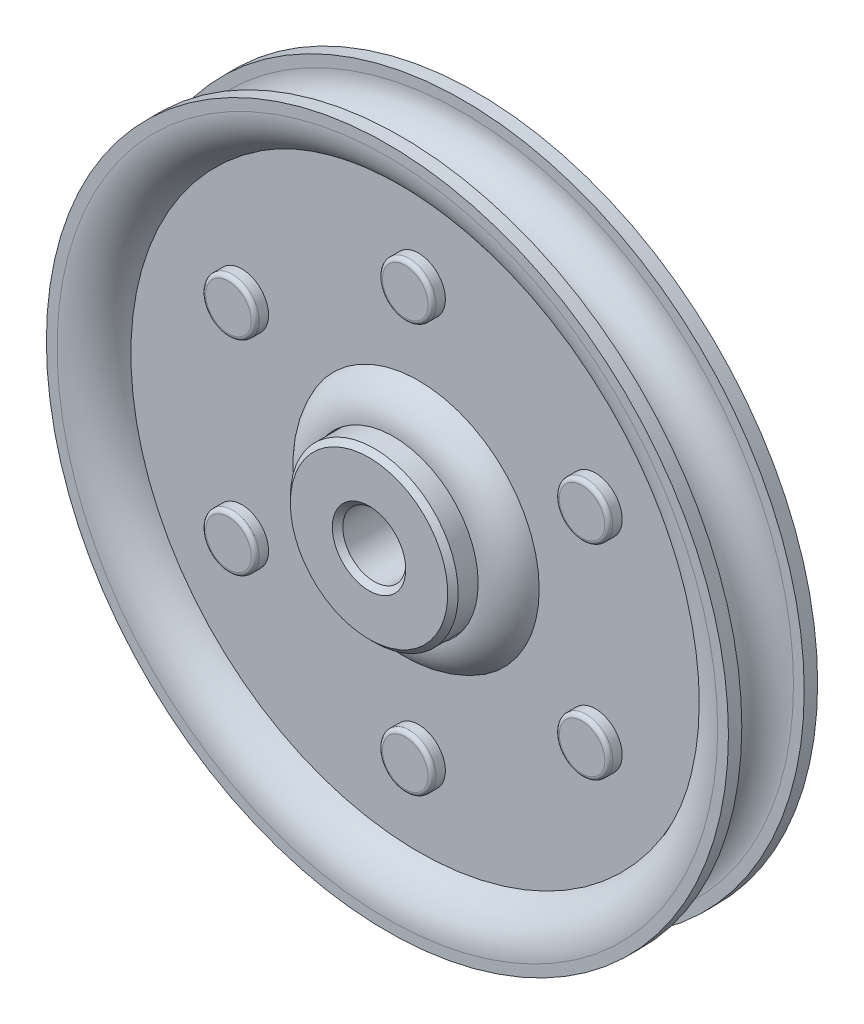
SolidWorks part; units mm, degrees
ref_plane "Front" through (0, 0, 0) normal (0, 0, 1) x (1, 0, 0)
ref_plane "Top" through (0, 0, 0) normal (0, 1, 0) x (1, 0, 0)
ref_plane "Right" through (0, 0, 0) normal (1, 0, 0) x (0, 0, -1)
sketch "Sketch1" plane through (0, 0, 0) normal (1, 0, 0) x (0, 0, -1)
  line L0 (4.7228, 51.5937) -> (6.7469, 51.5938)
  line L1 (-4.7228, 51.5938) -> (-6.7469, 51.5937)
  line L2 (-4.7228, 51.5938) -> (-4.7228, 49.9666)
  line L3 (1.9834, 12.827) -> (5.842, 12.827)
  line L4 (9.525, 4.7625) -> (-9.525, 4.7625)
  line L5 (-1.9834, 12.7) -> (-9.525, 12.7)
  line L6 (4.7228, 51.5937) -> (4.7228, 49.9666)
  line L7 (-6.7469, 51.5937) -> (-6.7469, 49.9666)
  line L8 (-9.525, 0) -> (9.525, 0) construction
  line L9 (-2.0241, 43.5305) -> (-2.0241, 18.244)
  line L10 (-2.0241, 43.5305) -> (0, 43.5305) construction
  line L11 (6.7469, 49.9666) -> (6.7469, 51.5938)
  line L12 (2.0241, 43.5305) -> (2.0241, 18.244)
  line L13 (-9.525, 12.7) -> (-9.525, 4.7625)
  line L14 (0, 45.2437) -> (0, -45.2437) construction
  line L16 (9.525, 12.7) -> (9.525, 4.7625)
  line L17 (-6.7469, 51.5937) -> (-6.7469, -51.5938) construction
  line L18 (-5.842, 12.827) -> (-1.9834, 12.827)
  line L20 (9.525, 12.7) -> (1.9834, 12.7)
  arc A0 (-4.7228, 49.9666) -> (4.7228, 49.9666) centre (0, 49.9666) ccw
  circle A1 centre (0, 49.9666) radius 4.7625 construction
  circle A2 centre (0, 0) radius 4.7625 construction
  circle A3 centre (0, 0) radius 12.7 construction
  arc A4 (-1.9834, 12.7) -> (1.9834, 12.7) centre (0, 12.7635) ccw
  circle A5 centre (0, -50.0063) radius 4.7625 construction
  arc A6 (1.9834, 12.827) -> (-1.9834, 12.827) centre (0, 12.7635) ccw
  arc A7 (-6.7469, 49.9666) -> (-2.0241, 43.5305) centre (0, 49.9666) ccw
  arc A8 (-5.842, 12.827) -> (-2.0241, 18.244) centre (0, 12.7635) cw
  arc A9 (2.0241, 43.5305) -> (6.7469, 49.9666) centre (0, 49.9666) ccw
  arc A10 (2.0241, 18.244) -> (5.842, 12.827) centre (0, 12.7635) cw
  point P28 (-6.7469, 0)
  point P42 (0, 10.7791)
  dimension "Rope Dia" = 9.525
  dimension "Shaft Dia" = 9.525
  dimension "bushin dia" = 25.4
  dimension "D2" = 3.9687
  dimension "Wd" = 19.05
  dimension "Groove Dia" = 90.4875
  dimension "OD" = 103.1875
  dimension "D3" = 0.127
  dimension "w Wd" = 13.4937
  dimension "D4" = 7.9375
  dimension "D5" = 10.7791
  dimension "D1" = 2.0241
  dimension "ball offset" = 5.842
revolve "Revolve1" add sketch "Sketch1" angle 360 about L8
sketch "Sketch2" plane through (0, 0, 0) normal (1, 0, 0) x (0, 0, -1)
  line L0 (0, 45.2437) -> (0, -45.2437) construction
  line L1 (0, 14.7479) -> (0, 10.7791)
  arc A0 (1.9834, 12.827) -> (-1.9834, 12.827) centre (0, 12.7635) ccw construction
  arc A1 (0, 10.7791) -> (0, 14.7479) centre (0, 12.7635) ccw
revolve "Revolve2" add sketch "Sketch2" angle 360 about L1
pattern_circular "CirPattern1" count 20 over 360 of bodies 117
chamfer "Chamfer1" distance 0.7937 angle 45 4 edges at (4.7625, 0, -9.525) (12.7, 0, -9.525) (12.7, 0, 9.525) (4.7625, 0, 9.525)
sketch "Sketch4" plane through (0, 0, 0) normal (1, 0, 0) x (0, 0, -1)
  line L0 (-2.0241, 32.9113) -> (2.0241, 32.9113)
  line L1 (2.0241, 32.9113) -> (2.0241, 34.9354)
  line L2 (2.0241, 34.9354) -> (4.0481, 34.9354)
  line L3 (4.0481, 34.9354) -> (4.0481, 30.8872)
  line L9 (-4.0481, 30.8872) -> (-4.0481, 34.9354)
  line L10 (-4.0481, 34.9354) -> (-2.0241, 34.9354)
  line L11 (-2.0241, 34.9354) -> (-2.0241, 32.9113)
  line L12 (-2.0241, 32.9113) -> (-2.0241, 30.8872) construction
  line L16 (-2.0241, 43.5305) -> (-2.0241, 18.244) construction
  line L17 (2.0241, 43.5305) -> (2.0241, 18.244) construction
  line L18 (-4.7228, 51.5938) -> (-6.7469, 51.5937) construction
  line L19 (-4.0481, 30.8872) -> (4.0481, 30.8872)
  dimension "D1" = 2.0241
revolve "Cut-Revolve2" cut sketch "Sketch4" angle 360 about L19
revolve "Revolve3" add sketch "Sketch4<2>" angle 360 about L19
sketch "Sketch4<2>" plane through (0, 0, 0) normal (1, 0, 0) x (0, 0, -1) same geometry as "Sketch4"
fillet "Fillet1" radius 0.6072 2 edges at (4.0481, 30.8872, -4.0481) (4.0481, 30.8872, 4.0481)
pattern_circular "CirPattern2" count 6 over 360 of "Cut-Revolve2"
pattern_circular "CirPattern3" count 6 over 360 of bodies 143
equation "\"D1@Chamfer1\" = \"D4@Sketch1\" * .1"
equation "\"D1@Sketch1\" = \"w Wd@Sketch1\" * .15"
equation "\"D1@Fillet1\" = \"D1@Sketch4\" * .3"
equation "\"D1@CirPattern3\" = \"stud count@CirPattern2\""
